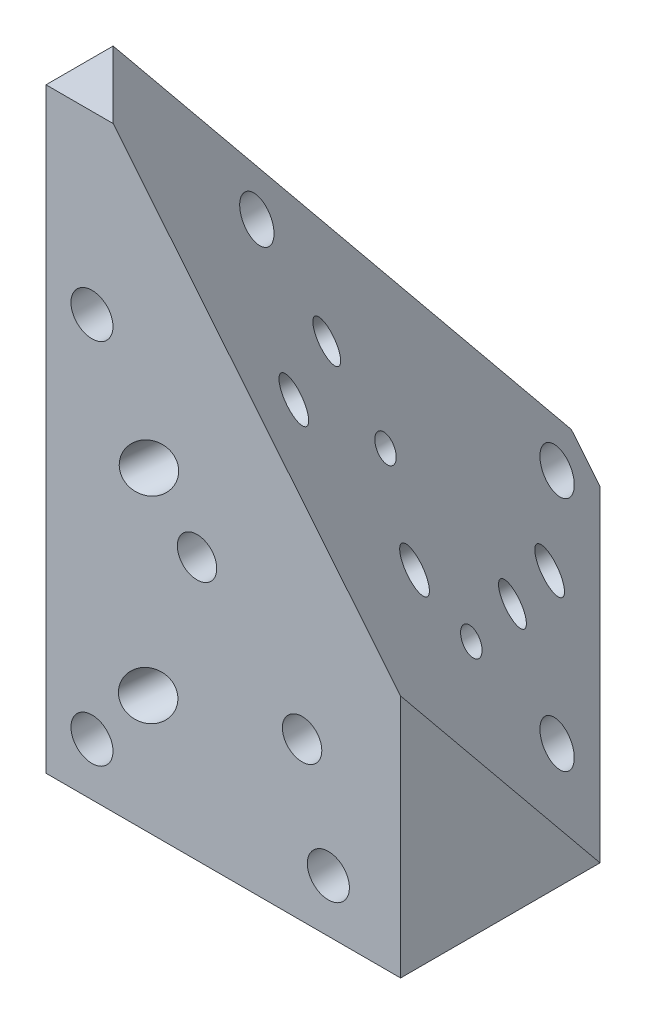
SolidWorks part; units mm, degrees
ref_plane "Front Plane" through (0, 0, 0) normal (0, 0, 1) x (1, 0, 0)
ref_plane "Top Plane" through (0, 0, 0) normal (0, 1, 0) x (1, 0, 0)
ref_plane "Right Plane" through (0, 0, 0) normal (1, 0, 0) x (0, 0, -1)
sketch "Sketch1" plane through (0, 0, 0) normal (0, 1, 0) x (1, 0, 0)
  line L0 (0, 0) -> (0, 20)
  line L2 (13.5, 0) -> (0, 0)
  line L3 (0, 20) -> (13.5, 20)
  line L4 (13.5, 20) -> (13.5, 0)
  dimension "D1" = 13.5
  dimension "D2" = 20
extrude "Boss-Extrude1" add sketch "Sketch1" along normal blind 22.7
ref_plane "Plane1" through (7.9092, 6.4578, -7.9092) normal (-0.6124, -0.5, 0.6124) x (0.7906, -0.3873, 0.4743)
sketch "Sketch2" plane through (7.9092, 6.4578, -7.9092) normal (-0.6124, -0.5, 0.6124) x (0.7906, -0.3873, 0.4743)
  line L1 (25.0062, -28.8765) -> (-25.0062, -28.8765)
  line L2 (25.0062, -28.8765) -> (25.0062, 28.8765)
  line L3 (25.0062, 28.8765) -> (-25.0062, 28.8765)
  line L4 (-25.0062, -28.8765) -> (-25.0062, 28.8765)
  line L5 (25.0062, -28.8765) -> (-25.0062, 28.8765) construction
  line L6 (25.0062, 28.8765) -> (-25.0062, -28.8765) construction
  point P0 (0, 0)
extrude "Cut-Extrude1" cut sketch "Sketch2" against normal through all
ref_plane "Plane2" through (-5.3897, 0, -5.3897) normal (-0.7071, 0, -0.7071) x (-0.7071, 0, 0.7071)
sketch "Sketch4" plane through (7.9092, 6.4578, -7.9092) normal (0.6124, 0.5, -0.6124) x (-0.4743, -0.3873, -0.7906)
  circle A0 centre (7.5975, -1.5053) radius 0.8 construction
  circle A1 centre (7.5975, -1.5053) radius 0.8 construction
  circle A2 centre (-6.516, 6.8355) radius 0.8 construction
  circle A3 centre (-3.5904, 1.0311) radius 0.8 construction
  circle A4 centre (-6.516, 6.8355) radius 0.8 construction
  circle A5 centre (-3.5904, 1.0311) radius 0.8 construction
hole_wizard "M2x0.4 Tapped Hole1" positions "3DSketch1" profile "Sketch5" tap size "M2x0.4" standard "ANSI Metric" end condition through all
sketch3d "3DSketch1"
  point P0 (6.6768, 14.2762, -2.7578)
  point P3 (8.9601, 8.6471, -5.0707)
  point P6 (5.2574, 2.3494, -13.9155)
sketch "Sketch5" plane through (6.6768, 14.2762, -2.7578) normal (0.4344, 0.4344, 0.7891) x (-0.6605, 0.7492, -0.0488)
  line L0 (0, 0) -> (0, 12.9156)
  line L1 (0, 12.9156) -> (0.8, 12.9156)
  line L2 (0.8, 12.9156) -> (0.8, 0)
  line L5 (0.8, 0) -> (0, 0)
  line L11 (0, -6.35) -> (0, 107.95) construction
  dimension "Thru Tap Drill Dia." = 1.6
  dimension "Thru Tap Drill Depth" = 12.9156
cosmetic thread "Hole Thread1" parameters "D2"=2
cosmetic thread "Hole Thread2" parameters "D2"=2
cosmetic thread "Hole Thread3" parameters "D2"=2
sketch "Sketch7" plane through (0, 0, 0) normal (0, 0, 1) x (1, 0, 0)
  circle A0 centre (10.75, 2) radius 1.2 construction
  circle A1 centre (10.75, 2) radius 1.2 construction
  circle A2 centre (1.75, 2) radius 1.2 construction
  circle A3 centre (1.75, 2) radius 1.2 construction
  circle A4 centre (1.75, 16) radius 1.2 construction
  circle A5 centre (1.75, 16) radius 1.2
hole_wizard "M2x0.4 Tapped Hole3" positions "3DSketch3" profile "Sketch9" tap size "M2x0.4" standard "ANSI Metric" end condition through all
sketch3d "3DSketch3"
  point P0 (1.75, 16, 0)
  point P3 (1.75, 2, 0)
  point P6 (10.75, 2, 0)
sketch "Sketch9" plane through (1.75, 16, 0) normal (1, 0, 0) x (0, -1, 0)
  line L0 (0, 0) -> (0, 20)
  line L1 (0, 20) -> (0.8, 20)
  line L2 (0.8, 20) -> (0.8, 0)
  line L5 (0.8, 0) -> (0, 0)
  line L11 (0, -6.35) -> (0, 107.95) construction
  dimension "Thru Tap Drill Dia." = 1.6
  dimension "Thru Tap Drill Depth" = 20
cosmetic thread "Hole Thread7" parameters "D1"=2.4, "D2"=2
cosmetic thread "Hole Thread8" parameters "D1"=2.4, "D2"=2
cosmetic thread "Hole Thread9" parameters "D1"=2.4, "D2"=2
sketch "Sketch10" plane through (0, 0, 0) normal (0, 0, 1) x (1, 0, 0)
  circle A0 centre (5.75, 10) radius 0.5 construction
  circle A1 centre (9.75, 6) radius 0.5 construction
  circle A2 centre (5.75, 10) radius 0.5 construction
  circle A3 centre (9.75, 6) radius 0.5 construction
hole_wizard "Ø1.0mm Dowel Hole1" positions "3DSketch4" profile "Sketch11" hole size "Ø1.0" standard "ANSI Metric" end condition through all
sketch3d "3DSketch4"
  point P0 (5.75, 10, 0)
  point P3 (9.75, 6, 0)
sketch "Sketch11" plane through (5.75, 10, 0) normal (1, 0, 0) x (0, -1, 0)
  line L0 (0, 0) -> (0, 20)
  line L1 (0, 20) -> (0.5, 20)
  line L2 (0.5, 20) -> (0.5, 0)
  line L5 (0.5, 0) -> (0, 0)
  line L11 (0, -6.35) -> (0, 107.95) construction
  dimension "Thru Hole Dia." = 1
  dimension "Thru Hole Depth" = 20
hole_wizard "Ø1.5mm Dowel Hole1" positions "3DSketch5" profile "Sketch13" hole size "Ø1.5" standard "ANSI Metric"
sketch3d "3DSketch5"
  point P0 (5.75, 10, 0)
  point P3 (9.75, 6, 0)
sketch "Sketch13" plane through (5.75, 10, 0) normal (1, 0, 0) x (0, -1, 0)
  line L0 (0, 0) -> (0, 4.9506)
  line L1 (0, 4.9506) -> (0.75, 4.5)
  line L2 (0.75, 4.5) -> (0.75, 0)
  line L5 (0.75, 0) -> (0, 0)
  line L10 (0, 4.9506) -> (-0.75, 4.5) construction
  line L11 (0, -6.35) -> (0, 107.95) construction
  dimension "Hole Dia." = 1.5
  dimension "Hole Depth" = 4.5
  dimension "Drill Angle" = 118
sketch "Sketch14" plane through (7.9092, 6.4578, -7.9092) normal (0.6124, 0.5, -0.6124) x (-0.4743, -0.3873, -0.7906)
  circle A0 centre (-1.3468, 7.439) radius 0.75 construction
  circle A1 centre (3.1253, -1.5053) radius 0.75 construction
  circle A2 centre (-1.3468, 7.439) radius 0.75 construction
  circle A3 centre (3.1253, -1.5053) radius 0.75 construction
hole_wizard "Ø1.0mm Dowel Hole2" positions "3DSketch6" profile "Sketch15" hole size "Ø1.0" standard "ANSI Metric" end condition through all
sketch3d "3DSketch6"
  point P0 (3.8432, 12.7417, -6.8444)
  point P3 (7.3787, 4.0814, -10.38)
sketch "Sketch15" plane through (3.8432, 12.7417, -6.8444) normal (0.4344, 0.4344, 0.7891) x (-0.6605, 0.7492, -0.0488)
  line L0 (0, 0) -> (0, 12.9156)
  line L1 (0, 12.9156) -> (0.5, 12.9156)
  line L2 (0.5, 12.9156) -> (0.5, 0)
  line L5 (0.5, 0) -> (0, 0)
  line L11 (0, -6.35) -> (0, 107.95) construction
  dimension "Thru Hole Dia." = 1
  dimension "Thru Hole Depth" = 12.9156
hole_wizard "Ø1.5mm Dowel Hole2" positions "3DSketch7" profile "Sketch16" hole size "Ø1.5" standard "ANSI Metric"
sketch3d "3DSketch7"
  point P0 (3.8432, 12.7417, -6.8444)
  point P3 (7.3787, 4.0814, -10.38)
sketch "Sketch16" plane through (3.8432, 12.7417, -6.8444) normal (0.4344, 0.4344, 0.7891) x (-0.6605, 0.7492, -0.0488)
  line L0 (0, 0) -> (0, 3.9506)
  line L1 (0, 3.9506) -> (0.75, 3.5)
  line L2 (0.75, 3.5) -> (0.75, 0)
  line L5 (0.75, 0) -> (0, 0)
  line L10 (0, 3.9506) -> (-0.75, 3.5) construction
  line L11 (0, -6.35) -> (0, 107.95) construction
  dimension "Hole Dia." = 1.5
  dimension "Hole Depth" = 3.5
  dimension "Drill Angle" = 118
